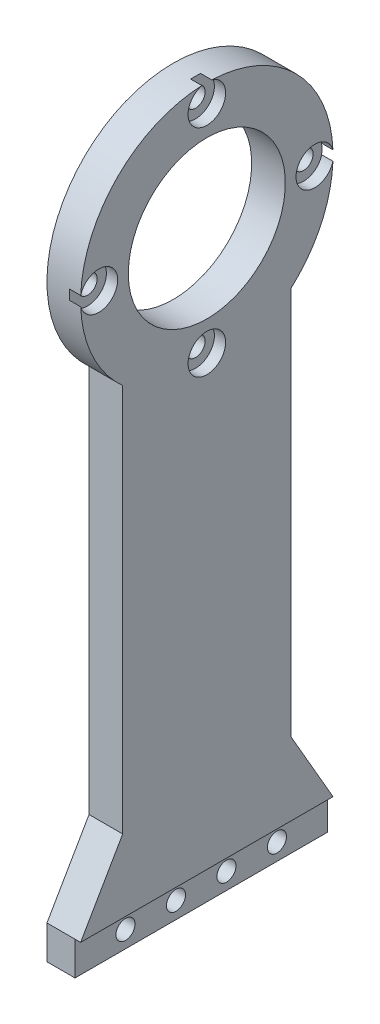
SolidWorks part; units mm, degrees
material "Сплав 2024"
ref_plane "Спереди" through (0, 0, 0) normal (0, 0, 1) x (1, 0, 0)
ref_plane "Сверху" through (0, 0, 0) normal (0, 1, 0) x (1, 0, 0)
ref_plane "Справа" through (0, 0, 0) normal (1, 0, 0) x (0, 0, -1)
sketch "Эскиз1" plane through (0, 0, 0) normal (0, 1, 0) x (1, 0, 0)
  line L1 (0, 0) -> (6, 0)
  line L2 (0, 0) -> (0, -30)
  line L3 (0, -30) -> (6, -30)
  line L4 (6, 0) -> (6, -30)
  dimension "D1" = 6
  dimension "D2" = 30
extrude "Бобышка-Вытянуть1" add sketch "Эскиз1" along normal blind 227
sketch "Эскиз2" plane through (0, 0, 0) normal (-1, 0, 0) x (0, 0, 1)
  line L0 (30, 105) -> (0, 105) construction
  line L3 (15, 227) -> (15, 0) construction
  line L4 (0, 227) -> (30, 227) construction
  line L5 (0, 0) -> (30, 0) construction
  line L6 (30, 0) -> (0, 0) construction
  circle A0 centre (15, 105) radius 22.5
  dimension "D1" = 45
  dimension "D2" = 105
extrude "Бобышка-Вытянуть2" add sketch "Эскиз2" against normal up to surface (6 mm away) up to face at (6, 113.5, 15)
sketch "Эскиз3" plane through (0, 0, 0) normal (-1, 0, 0) x (0, 0, 1)
  circle A0 centre (15, 105) radius 14
  dimension "D1" = 28
extrude "Вырез-Вытянуть1" cut sketch "Эскиз3" against normal through all
sketch "Эскиз4" plane through (6, 0, 0) normal (-1, 0, 0) x (0, 0, 1)
  line L0 (15, 127.5) -> (15, 82.5) construction
  line L1 (15, 227) -> (15, 0) construction
  line L2 (37.5, 105) -> (-7.5, 105) construction
  circle A0 centre (15, 105) radius 19.25 construction
  circle A1 centre (15, 105) radius 22.5 construction
  dimension "D1" = 38.5
hole_wizard "Цековка для  винта с полукруглой головкой M31" positions "Эскиз6" profile "Эскиз5" counterbore size "M3" standard "Ansi Metric" end condition through all
sketch "Эскиз6" plane through (6, -25.0247, 7.2629) normal (-1, 0, 0) x (0, 0, 1)
  line L0 (7.7371, 152.5247) -> (7.7371, 107.5247) construction
  line L1 (30.2371, 130.0247) -> (-14.7629, 130.0247) construction
  circle A0 centre (7.7371, 130.0247) radius 19.25 construction
  point P0 (7.7371, 149.2747)
  point P6 (-11.5129, 130.0247)
  point P10 (7.7371, 110.7747)
  point P12 (26.9871, 130.0247)
sketch "Эскиз5" plane through (6, 124.25, 15) normal (0, 1, 0) x (0, 0, -1)
  line L0 (0, 0) -> (0, 6)
  line L1 (0, 6) -> (1.7, 6)
  line L3 (1.7, 6) -> (1.7, 2)
  line L4 (1.7, 2) -> (3.35, 2)
  line L5 (3.35, 2) -> (3.35, 0)
  line L7 (3.35, 0) -> (0, 0)
  line L11 (0, -6.35) -> (0, 107.95) construction
  dimension "Диаметр сквозного отверстия" = 3.4
  dimension "Глубина сквозного отверстия" = 6
  dimension "Диаметр цековки" = 6.7
  dimension "Глубина цековки" = 2
sketch "Эскиз8" plane through (6, 0, 0) normal (1, 0, 0) x (0, 0, -1)
  line L0 (-15, 227) -> (-15, 0) construction
  line L1 (-30, 227) -> (0, 227) construction
  line L2 (-30, 0) -> (0, 0) construction
  line L3 (19.447, 105) -> (-49.447, 105) construction
  line L4 (0, 227) -> (0, 121.7705) construction
  line L5 (-26, 145) -> (-4, 145) construction
  line L6 (-26, 145) -> (-26, 65) construction
  line L7 (-26, 65) -> (-4, 65) construction
  line L8 (-4, 145) -> (-4, 65) construction
  line L9 (-26, 145) -> (-4, 65) construction
  line L10 (-26, 65) -> (-4, 145) construction
  point P8 (-15, 105)
  point P9 (-15, 105)
  dimension "D1" = 4
  dimension "D2" = 80
  dimension "D3" = 105
sketch "Эскиз11" plane through (6, 0, 0) normal (1, 0, 0) x (0, 0, -1)
  line L0 (-30, 0) -> (0, 0) construction
  line L1 (-15, 227) -> (-15, 0) construction
  line L2 (-30, 227) -> (0, 227) construction
  line L3 (0, 88.2295) -> (0, 0) construction
  line L4 (-30, 88.2295) -> (-30, 0) construction
  line L5 (-37.5, 3) -> (7.5, 3) construction
  line L20 (-1.5, 0) -> (-1.5, 6) construction
  line L21 (-10.5, 0) -> (-10.5, 6) construction
  line L22 (-19.5, 0) -> (-19.5, 6) construction
  line L23 (-28.5, 0) -> (-28.5, 6) construction
  line L25 (-37.5, 0) -> (7.5, 6) construction
  line L26 (-37.5, 6) -> (7.5, 0) construction
  line L27 (-37.5, 6) -> (7.5, 6) construction
  line L28 (0, 18.9904) -> (7.5, 6)
  line L29 (-30, 18.9904) -> (0, 18.9904)
  line L30 (7.5, 6) -> (7.5, 0)
  line L31 (-37.5, 0) -> (7.5, 0)
  line L32 (-37.5, 6) -> (-37.5, 0)
  line L33 (-37.5, 6) -> (-30, 18.9904)
  point P2 (-15, 3)
  dimension "D1" = 45
  dimension "D2" = 6
  dimension "D3" = 9
  dimension "D4" = 9
  dimension "D5" = 9
  dimension "D6" = 9
  dimension "D7" = 120
extrude "Бобышка-Вытянуть3" add sketch "Эскиз11" against normal up to surface (6 mm away) up to face at (0, 124.25, 13.3)
hole_wizard "Отверстие с зазором M31" positions "Эскиз13" profile "Эскиз12" hole size "M3" standard "Ansi Metric" end condition through all
sketch "Эскиз13" plane through (6, 0, 0) normal (1, 0, 0) x (0, 0, -1)
  line L4 (-28.5, 0) -> (-28.5, 6) construction
  line L5 (-19.5, 0) -> (-19.5, 6) construction
  line L6 (-10.5, 0) -> (-10.5, 6) construction
  line L7 (-1.5, 0) -> (-1.5, 6) construction
  point P16 (-28.5, 3)
  point P20 (-19.5, 3)
  point P24 (-10.5, 3)
  point P28 (-1.5, 3)
sketch "Эскиз12" plane through (6, 3, 28.5) normal (0, 1, 0) x (0, 0, -1)
  line L0 (0, 0) -> (0, 6)
  line L1 (0, 6) -> (1.7, 6)
  line L2 (1.7, 6) -> (1.7, 0)
  line L5 (1.7, 0) -> (0, 0)
  line L11 (0, -6.35) -> (0, 107.95) construction
  dimension "Диаметр сквозного отверстия" = 3.4
  dimension "Глубина сквозного отверстия" = 6
sketch "Эскиз14" plane through (6, 0, 0) normal (1, 0, 0) x (0, 0, -1)
  line L5 (-37.5, 0) -> (7.5, 0)
  line L6 (-37.5, 0) -> (-37.5, 6)
  line L7 (-37.5, 6) -> (7.5, 6)
  line L8 (7.5, 0) -> (7.5, 6)
extrude "Вырез-Вытянуть2" cut sketch "Эскиз14" against normal blind 1
sketch "Эскиз15" plane through (6, 0, 0) normal (1, 0, 0) x (0, 0, -1)
  line L0 (0, 227) -> (0, 121.7705) construction
  line L1 (-30, 227) -> (0, 227)
  line L2 (-30, 227) -> (-30, 121.7705)
  line L4 (0, 227) -> (0, 121.7705)
  arc A1 (-30, 121.7705) -> (0, 121.7705) centre (-15, 105) cw
extrude "Вырез-Вытянуть3" cut sketch "Эскиз15" against normal up to surface (6 mm away) up to face at (0, 3, 26.8)
equation "\"D4@Эскиз11\"=\"D3@Эскиз11\""
equation "\"D5@Эскиз11\"=\"D3@Эскиз11\""
equation "\"D6@Эскиз11\"=\"D4@Эскиз11\""
equation "\"D3@Эскиз11\" = \"D1@Эскиз11\" / 5"
